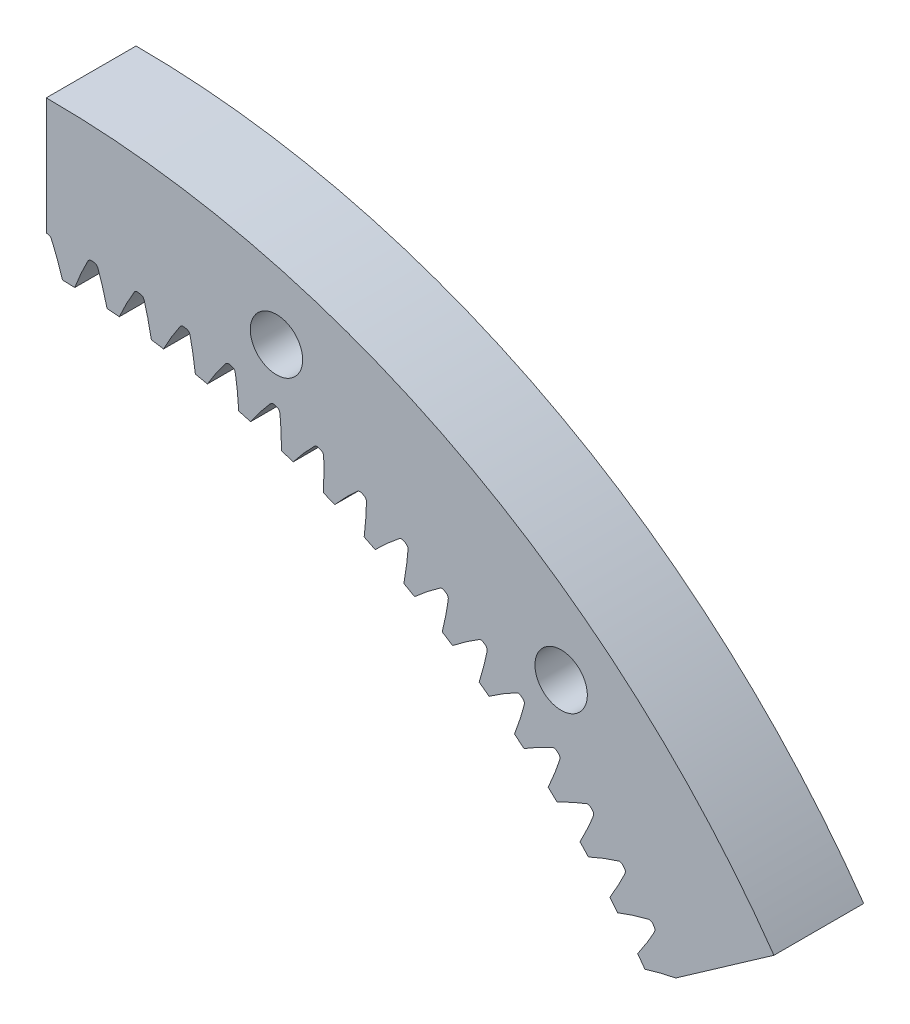
SolidWorks part; units mm, degrees
material "Д16 ГОСТ 4784-97"
ref_plane "FRONT" through (0, 0, 0) normal (0, 0, 1) x (1, 0, 0)
ref_plane "TOP" through (0, 0, 0) normal (0, 1, 0) x (1, 0, 0)
ref_plane "RIGHT" through (0, 0, 0) normal (1, 0, 0) x (0, 0, -1)
ref_axis "Ось1" through (0, 0, 50) along (0, 0, -1)
sketch "SketchRevolveSpurAssemblyNew2Gear" plane through (0, 0, 0) normal (1, 0, 0) x (0, 0, -1)
  line L0 (0, 0) -> (1, 0) construction
  line L1 (-2, 49.399) -> (-2, 59.399)
  line L2 (-2, 59.399) -> (4, 59.399)
  line L3 (4, 59.399) -> (4, 49.399)
  line L4 (4, 49.399) -> (-2, 49.399)
  dimension "MinorDiameter" = 49.399
  dimension "D1" = 6
  dimension "D2" = 10
revolve "SpurAssemblyNew2Gear" add sketch "SketchRevolveSpurAssemblyNew2Gear" angle 360 about L0
sketch "SketchToothSpurAssemblyNew2Gear" plane through (0, 0, 0) normal (0, 0, 1) x (1, 0, 0)
  arc A0 (49.1395, -1.1537) -> (49.1395, 1.1537) centre (0, 0) ccw
  spline S0 degree 3 poles (49.1395, 1.1537) (49.2861, 1.1124) (49.5102, 1.0454) (49.8138, 0.9473) (50.0554, 0.8652) (50.306, 0.7758) (50.5651, 0.6788) (50.8329, 0.5746) (51.108, 0.4599) (51.3094, 0.3804) (51.4272, 0.3224) (51.4611, 0.2973) (51.4911, 0.268) (51.5164, 0.2347) (51.5367, 0.198) (51.5565, 0.1461) (51.5633, 0.0916) (51.5623, 0.0385) (51.5626, 0) (51.5623, -0.0385) (51.5633, -0.0916) (51.5565, -0.1461) (51.5367, -0.198) (51.5164, -0.2347) (51.4911, -0.268) (51.4611, -0.2973) (51.4272, -0.3224) (51.3094, -0.3804) (51.108, -0.4599) (50.8329, -0.5746) (50.5651, -0.6788) (50.306, -0.7758) (50.0554, -0.8652) (49.8138, -0.9473) (49.5102, -1.0454) (49.2861, -1.1124) (49.1395, -1.1537) knots 0 0 0 0 0.081489 0.125094 0.170606 0.218025 0.26735 0.318583 0.371722 0.426768 0.434365 0.441808 0.449251 0.456695 0.464138 0.471581 0.486277 0.493139 0.5 0.506861 0.513723 0.528419 0.535862 0.543305 0.550749 0.558192 0.565635 0.573232 0.628278 0.681417 0.73265 0.781975 0.829394 0.874906 0.918511 1 1 1 1
extrude "ToothExtrudeCutSpurAssemblyNew2Gear" cut sketch "SketchToothSpurAssemblyNew2Gear" against normal blind 4 and the other way blind 4
pattern_circular "PatternSpurAssemblyNew2Gear" count 104 every 3.462 about axis through (0, 0, 50) along (0, 0, -1) of "ToothExtrudeCutSpurAssemblyNew2Gear"
sketch "AuxiliarySketchSpurAssemblyNew2Gear" plane through (0, 0, 0) normal (0, 0, 1) x (1, 0, 0)
  circle A0 centre (0, 0) radius 50 construction
  circle A1 centre (0, 0) radius 46.9846 construction
  circle A2 centre (0, 0) radius 51.5625 construction
  circle A3 centre (0, 0) radius 49.399 construction
  dimension "PitchDiameter" = 100
  dimension "BaseDiameter" = 93.9693
  dimension "MajorDiameter" = 103.125
  dimension "MinorDiameter" = 98.7981
sketch "Эскиз1" plane through (0, 0, 2) normal (0, 0, 1) x (1, 0, 0)
  line L0 (0, 0) -> (0, 72.3035)
  line L1 (0, 0) -> (59.2276, 41.4716)
  line L2 (0, 0) -> (25.3962, 48.7856) construction
  line L3 (0, 0) -> (15.3906, 52.8027) construction
  arc A0 (0, 72.3035) -> (59.2276, 41.4716) centre (0, 0) ccw
  arc A1 (45.0534, 31.5467) -> (0, 55) centre (0, 0) ccw construction
  circle A2 centre (15.3906, 52.8027) radius 1.75
  arc A3 (20.7548, 14.5327) -> (0, 25.337) centre (0, 0) ccw construction
  circle A4 centre (34.4258, 42.8936) radius 1.75
  point P8 (25.3962, 48.7856)
  point P9 (11.6993, 22.4742)
  dimension "D2" = 11.25
  dimension "D3" = 25.337
  dimension "D4" = 3.5
  dimension "D5" = 110
  dimension "D1" = 55
extrude "Вырез-Вытянуть1" cut sketch "Эскиз1" against normal through all
